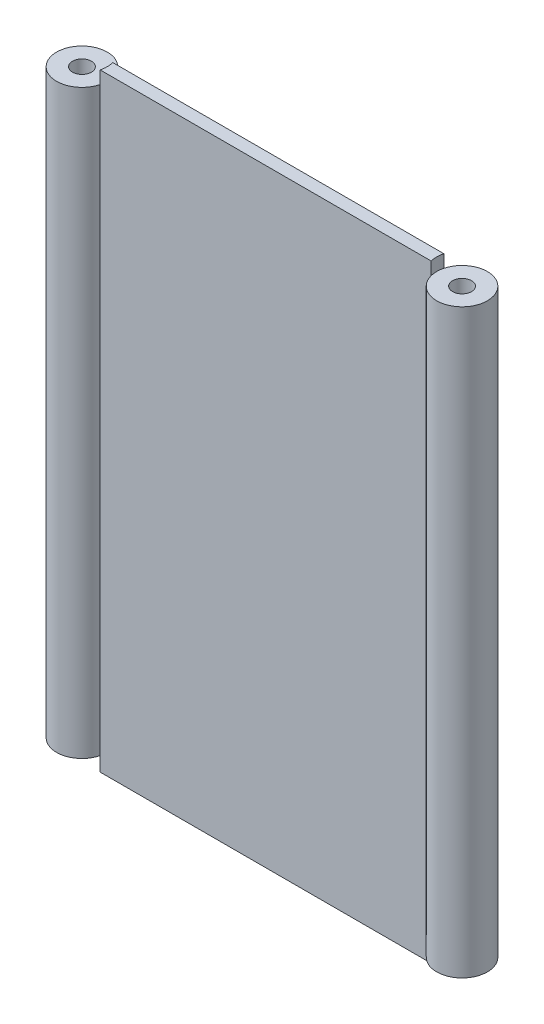
SolidWorks part; units mm, degrees
ref_plane "Front Plane" through (0, 0, 0) normal (0, 0, 1) x (1, 0, 0)
ref_plane "Top Plane" through (0, 0, 0) normal (0, 1, 0) x (1, 0, 0)
ref_plane "Right Plane" through (0, 0, 0) normal (1, 0, 0) x (0, 0, -1)
sketch "Sketch1" plane through (0, 0, 0) normal (0, 1, 0) x (1, 0, 0)
  line L0 (0, 0) -> (-41.4766, 0) construction
  line L1 (-41.4766, 3.175) -> (0, 3.175)
  line L2 (-41.4766, 0) -> (0, 0)
  line L7 (0, 3.175) -> (0, 0)
  line L8 (-41.4766, 3.175) -> (-41.4766, 0) construction
  line L9 (-47.625, 1.5875) -> (-41.275, 1.5875) construction
  circle A1 centre (-47.625, 1.5875) radius 2.3812
  arc A3 (-41.4766, 3.175) -> (-41.4766, 0) centre (-47.625, 1.5875) ccw
  dimension "D4" = 4.7625
  dimension "D5" = 6.35
  dimension "D2" = 12.7
  dimension "D3" = 3.175
extrude "Boss-Extrude1" add sketch "Sketch1" along normal blind 152.4 contours L2 L7 L1 A3 | A1
sketch "Sketch2" plane through (0, 0, 0) normal (0, -1, 0) x (1, 0, 0)
  circle A2 centre (-47.625, -1.5875) radius 6.35
extrude "Cut-Extrude1" cut sketch "Sketch2" against normal blind 3.5719
sketch "Sketch3" plane through (0, 152.4, 0) normal (0, 1, 0) x (1, 0, 0)
  circle A2 centre (-47.625, 1.5875) radius 6.35
extrude "Cut-Extrude3" cut sketch "Sketch3" against normal blind 3.175
mirror "Mirror2" about plane through (0, 152.4, -3.175) normal (1, 0, 0) of "Boss-Extrude1", "Cut-Extrude1", "Cut-Extrude3"
